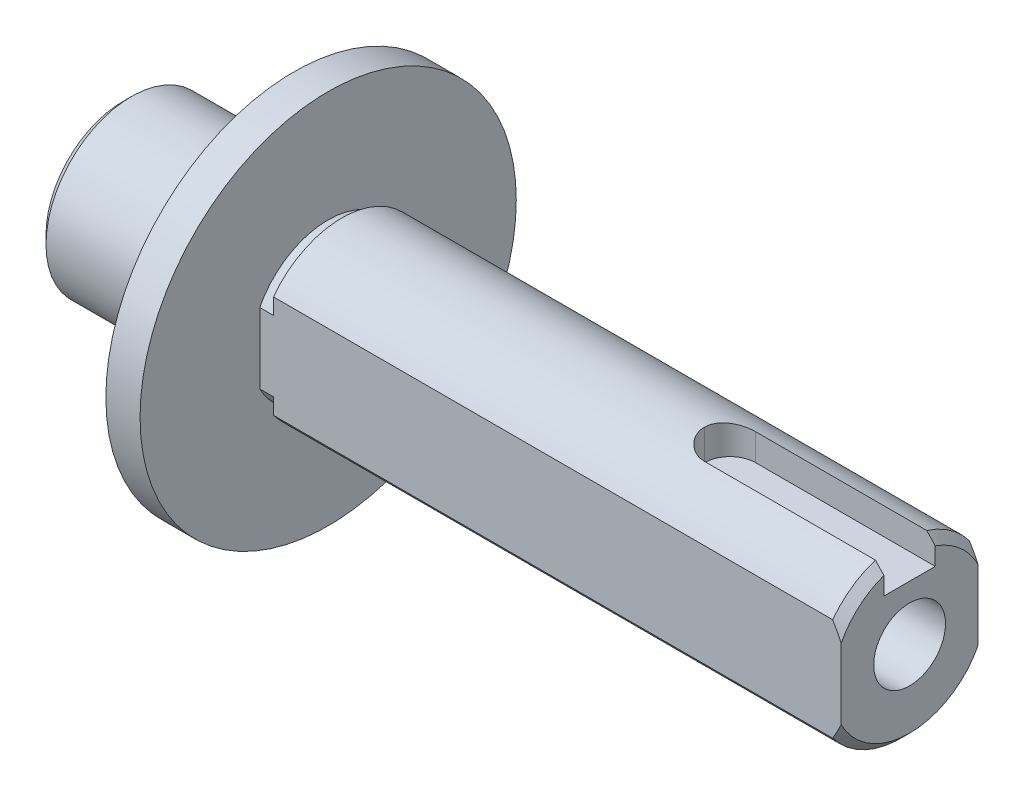
SolidWorks part; units mm, degrees
material "6061-T6 (SS)"
ref_plane "Front Plane" through (0, 0, 0) normal (0, 0, 1) x (1, 0, 0)
ref_plane "Top Plane" through (0, 0, 0) normal (0, 1, 0) x (1, 0, 0)
ref_plane "Right Plane" through (0, 0, 0) normal (1, 0, 0) x (0, 0, -1)
sketch "Sketch1" plane through (0, 0, 0) normal (1, 0, 0) x (0, 0, -1)
  circle A0 centre (0, 0) radius 5
  dimension "D1" = 10
extrude "Boss-Extrude1" add sketch "Sketch1" along normal blind 34
chamfer "Chamfer1" distance 0.5 angle 45 1 edges at (34, 0, -5)
sketch "Sketch2" plane through (0, 0, 0) normal (-1, 0, 0) x (0, 0, 1)
  circle A0 centre (0, 0) radius 11
  dimension "D1" = 22
extrude "Boss-Extrude2" add sketch "Sketch2" along normal blind 2
sketch "Sketch3" plane through (34, 0, 0) normal (1, 0, 0) x (0, 0, -1)
  line L0 (0, 0) -> (0, 3.2) construction
  line L1 (-1.5, 5) -> (1.5, 5)
  line L2 (-1.5, 5) -> (-1.5, 3.2)
  line L3 (-1.5, 3.2) -> (1.5, 3.2)
  line L4 (1.5, 5) -> (1.5, 3.2)
  line L5 (0, 0) -> (8.3936, 0) construction
  line L6 (-1.5, -3.2) -> (1.5, -3.2)
  line L7 (1.5, -5) -> (1.5, -3.2)
  line L8 (-1.5, -5) -> (1.5, -5)
  line L9 (-1.5, -5) -> (-1.5, -3.2)
  circle A0 centre (0, 0) radius 5 construction
  dimension "D1" = 3
  dimension "D2" = 1.8
extrude "Cut-Extrude1" cut sketch "Sketch3" against normal blind 12 contours L3 L4 L1 L2
fillet "Fillet1" radius 1.5 2 edges at (22, 3.9848, 1.5) (22, 3.9848, -1.5)
sketch "Sketch4" plane through (-2, 0, 0) normal (-1, 0, 0) x (0, 0, 1)
  circle A0 centre (0, 0) radius 5
  dimension "D1" = 10
extrude "Boss-Extrude3" add sketch "Sketch4" along normal blind 10
sketch "Sketch6" plane through (0, 0, 0) normal (0, 0, 1) x (1, 0, 0)
  line L0 (0, 0) -> (37.6174, 0) construction
  line L1 (-2, 5) -> (-2.8, 5)
  line L2 (-2, 5) -> (-2, 4.5)
  line L3 (-2, 4.5) -> (-2.8, 4.5)
  line L4 (-2.8, 5) -> (-2.8, 4.5)
  line L6 (0, 5) -> (0.8, 5)
  line L7 (0, 5) -> (0, 4.5)
  line L8 (0, 4.5) -> (0.8, 4.5)
  line L9 (0.8, 5) -> (0.8, 4.5)
  dimension "D1" = 0.8
  dimension "D2" = 0.5
revolve "Cut-Revolve1" cut sketch "Sketch6" angle 360 about L0
ref_plane "Plane1" through (1, 0, 0) normal (1, 0, 0) x (0, 0, -1)
chamfer "Chamfer2" distance 0.5 angle 45 1 edges at (-12, 0, 5)
sketch "Sketch7" plane through (0, 0, 0) normal (1, 0, 0) x (0, 0, -1)
  line L6 (-4, 3) -> (-4, -3)
  line L8 (4, 3) -> (4, -3)
  circle A3 centre (0, 0) radius 5 construction
  arc A4 (-4, 3) -> (-4, -3) centre (0, 0) ccw
  arc A5 (4, -3) -> (4, 3) centre (0, 0) ccw
  dimension "D1" = 8
extrude "Cut-Extrude2" cut sketch "Sketch7" along normal through all
sketch "Sketch10" plane through (34, 0, 0) normal (1, 0, 0) x (0, 0, -1)
  point P0 (0, 0)
hole_wizard "Tap Drill for M4 Helicoil1" positions "Sketch10" profile "Sketch11" hole size "M4x0.7" standard "DIN"
sketch "Sketch11" plane through (34, 0, 0) normal (0, 1, 0) x (0, 0, -1)
  line L0 (0, 0) -> (0, 21.2618)
  line L1 (0, 21.2618) -> (2.1, 20)
  line L2 (2.1, 20) -> (2.1, 0)
  line L5 (2.1, 0) -> (0, 0)
  line L10 (0, 21.2618) -> (-2.1, 20) construction
  line L11 (0, -6.35) -> (0, 107.95) construction
  dimension "Hole Dia." = 4.2
  dimension "Hole Depth" = 20
  dimension "Drill Angle" = 118
